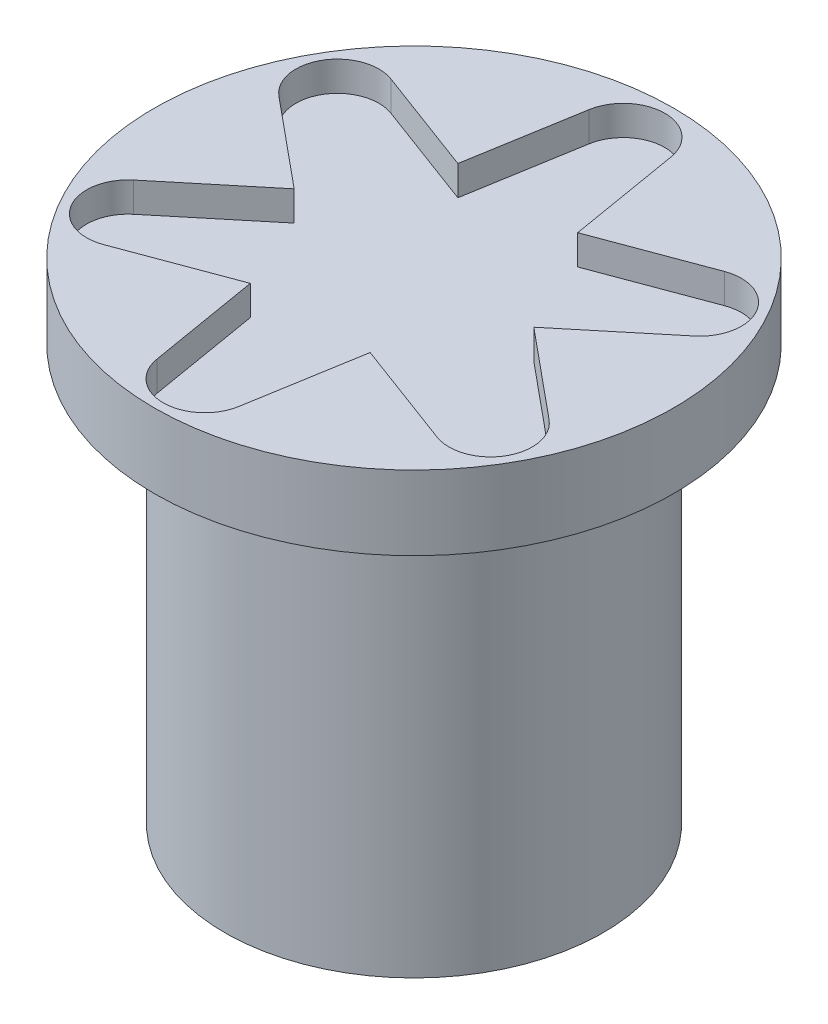
SolidWorks part; units mm, degrees
material "PBT General Purpose"
ref_plane "Front Plane" through (0, 0, 0) normal (0, 0, 1) x (1, 0, 0)
ref_plane "Top Plane" through (0, 0, 0) normal (0, 1, 0) x (1, 0, 0)
ref_plane "Right Plane" through (0, 0, 0) normal (1, 0, 0) x (0, 0, -1)
sketch "Sketch1" plane through (0, 0, 0) normal (0, 1, 0) x (1, 0, 0)
  line L0 (4, 12.1063) -> (4, 7.7822)
  line L5 (-2, 3.8) -> (2, 3.8)
  line L6 (-2, -3.8) -> (2, -3.8)
  line L12 (-12.1063, -4) -> (-7.7822, -4)
  arc A0 (-12.1063, -4) -> (4, 12.1063) centre (0, 0) ccw
  arc A2 (4, 7.7822) -> (-7.7822, -4) centre (0, 0) ccw
  arc A3 (-2, 3.8) -> (-2, -3.8) centre (-2, 0) ccw
  arc A4 (2, -3.8) -> (2, 3.8) centre (2, 0) ccw
  point P0 (0, 0)
  point P2 (-5.8, 0)
  point P4 (5.8, 0)
  point P10 (0, 0)
  dimension "D3" = 25.5
  dimension "D4" = 17.5
  dimension "D1" = 11.6
  dimension "D2" = 7.6
  dimension "D5" = 4
  dimension "D6" = 4
  dimension "D7" = 3.8
  dimension "D8" = 5.8
extrude "Boss-Extrude1" add sketch "Sketch1" against normal blind 3
sketch "Sketch2" plane through (0, 0, 0) normal (0, 1, 0) x (1, 0, 0)
  line L0 (-7.7822, -4) -> (-12.1063, -4) construction
  line L1 (-8.8917, -4) -> (-12.1063, -4)
  line L2 (4, 12.1063) -> (4, 7.7822) construction
  line L3 (4, 12.1063) -> (4, 8.8917)
  arc A0 (-8.8917, -4) -> (4, 8.8917) centre (0, 0) ccw
  arc A1 (-12.1063, -4) -> (4, 12.1063) centre (0, 0) ccw construction
  arc A2 (-12.1063, -4) -> (4, 12.1063) centre (0, 0) ccw
  dimension "D1" = 19.5
extrude "Boss-Extrude2" add sketch "Sketch2" along normal blind 25
sketch "Sketch3" plane through (0, 25, 0) normal (0, 1, 0) x (1, 0, 0)
  circle A0 centre (0, 0) radius 17.5
  dimension "D1" = 35
extrude "Boss-Extrude3" add sketch "Sketch3" along normal blind 5
sketch "Sketch4" plane through (0, 30, 0) normal (0, 1, 0) x (1, 0, 0)
  line L0 (-2.7611, 14.5654) -> (-4.0973, 6.6372)
  line L1 (2.7611, 14.5654) -> (4.0973, 6.6372)
  arc A0 (-4.0973, 6.6372) -> (4.0973, 6.6372) centre (0, 0) ccw
  arc A1 (2.7611, 14.5654) -> (-2.7611, 14.5654) centre (0, 14.1) ccw
  dimension "D1" = 15.6
  dimension "D2" = 5.6
  dimension "D3" = 14.1
  dimension "D4" = 8.04
  dimension "D5" = 8.04
extrude "Cut-Extrude1" cut sketch "Sketch4" against normal blind 2
pattern_circular "CirPattern1" count 6 over 360 about axis through (0, 28, 0) along (0, 1, 0) of "Cut-Extrude1"
